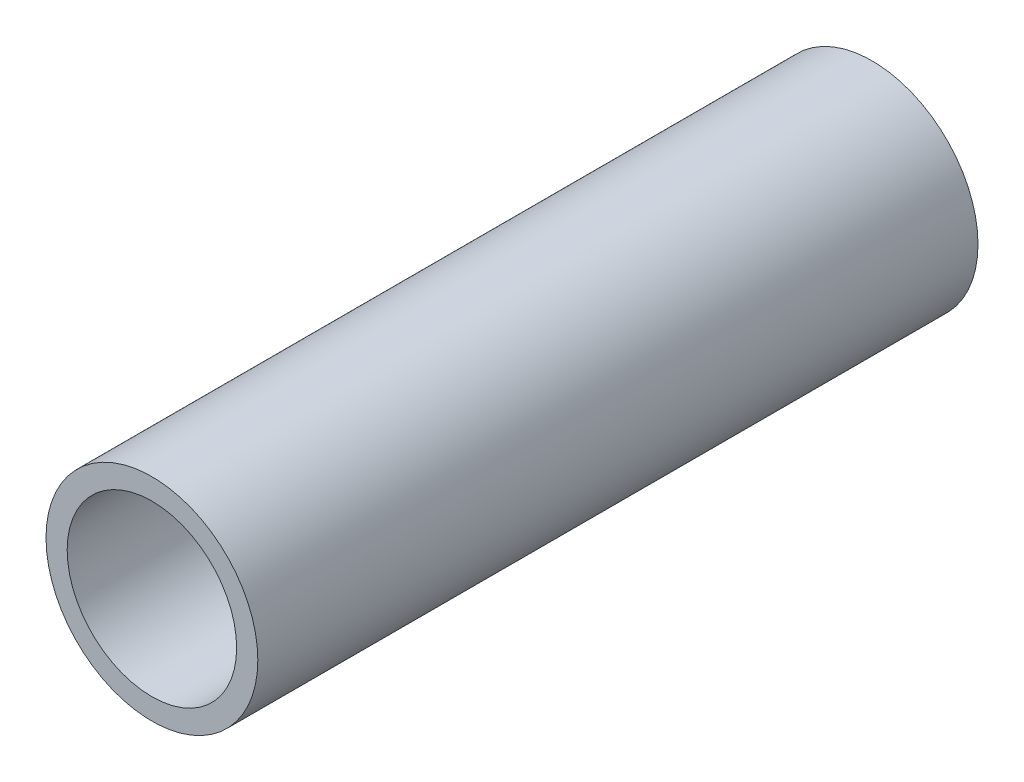
SolidWorks part; units mm, degrees
material "Nylon 101"
ref_plane "Front Plane" through (0, 0, 0) normal (0, 0, 1) x (1, 0, 0)
ref_plane "Top Plane" through (0, 0, 0) normal (0, 1, 0) x (1, 0, 0)
ref_plane "Right Plane" through (0, 0, 0) normal (1, 0, 0) x (0, 0, -1)
sketch "Sketch1" plane through (0, 0, 0) normal (0, 0, 1) x (1, 0, 0)
  circle A0 centre (0, 0) radius 6.35
  circle A1 centre (0, 0) radius 7.9375
  dimension "D1" = 12.7
  dimension "D2" = 15.875
extrude "Boss-Extrude1" add sketch "Sketch1" along normal mid plane 53.975
